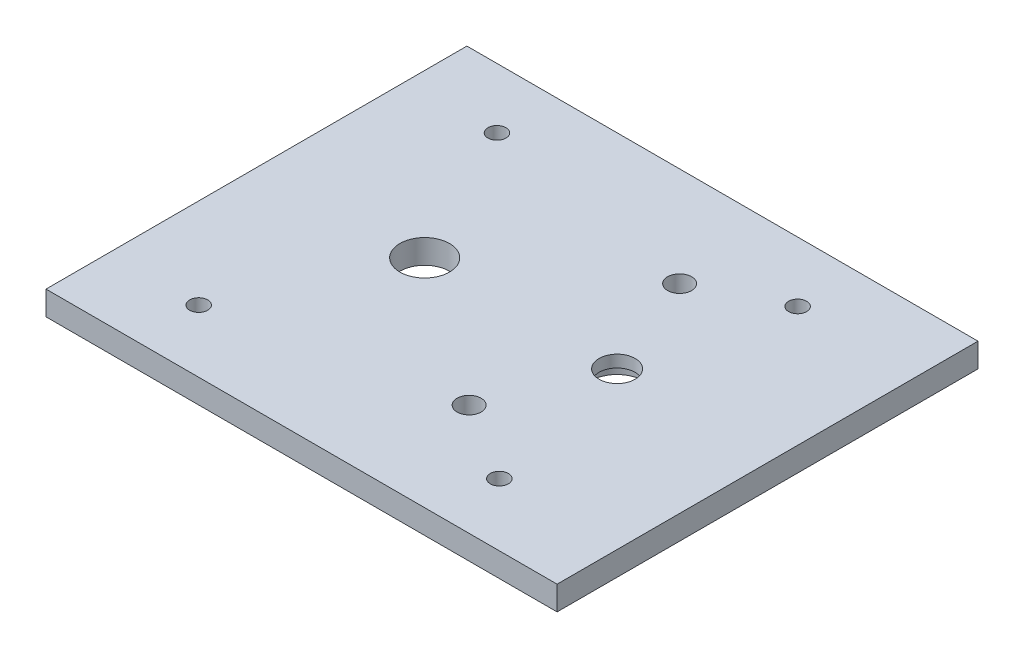
SolidWorks part; units mm, degrees
ref_plane "Front Plane" through (0, 0, 0) normal (0, 0, 1) x (1, 0, 0)
ref_plane "Top Plane" through (0, 0, 0) normal (0, 1, 0) x (1, 0, 0)
ref_plane "Right Plane" through (0, 0, 0) normal (1, 0, 0) x (0, 0, -1)
sketch "Sketch1" plane through (0, 0, 0) normal (0, 1, 0) x (1, 0, 0)
  line L0 (0, 8.2993) -> (0, -7.906) construction
  line L1 (-42.5, 35) -> (42.5, 35)
  line L2 (-42.5, 35) -> (-42.5, -35)
  line L3 (-42.5, -35) -> (42.5, -35)
  line L4 (42.5, 35) -> (42.5, -35)
  line L5 (-42.5, 35) -> (42.5, -35) construction
  line L6 (-42.5, -35) -> (42.5, 35) construction
  line L7 (-12.4915, 0.1967) -> (14.4413, 0.1967) construction
  line L8 (9.5, 1) -> (10.7497, 1) construction
  line L9 (37.5085, 0.1967) -> (64.4413, 0.1967) construction
  line L11 (15.0001, 2.9838) -> (15.0001, -1.0162)
  line L13 (17.9999, 3.0162) -> (17.9999, -0.9838)
  line L14 (15.0001, 2.9838) -> (17.9999, -0.9838) construction
  line L15 (15.0001, -1.0162) -> (17.9999, 3.0162) construction
  circle A0 centre (-27.5, 25) radius 1.5
  circle A1 centre (22.5, 25) radius 1.5
  circle A2 centre (22.5, -24.6067) radius 1.5
  circle A3 centre (-27.5, -24.6067) radius 1.5
  circle A4 centre (16.5, 1) radius 10
  circle A5 centre (-15.52, 1) radius 20
  arc A6 (15.0001, 2.9838) -> (17.9999, 3.0162) centre (16.5217, 1.0001) cw
  arc A7 (15.0001, -1.0162) -> (17.9999, -0.9838) centre (16.4783, 0.9999) ccw
  circle A8 centre (16.4783, 0.9999) radius 4.5
  circle A12 centre (-15.52, 1) radius 4.125
  circle A13 centre (16.4783, 0.9999) radius 3
  circle A14 centre (9.5, 1) radius 14
  circle A17 centre (85.0307, -10.8481) radius 14
  circle A18 centre (86.1334, -28.3481) radius 2
  circle A19 centre (86.1334, 6.6519) radius 2
  circle A20 centre (9.5, 1) radius 14
  circle A21 centre (9.4072, 18.471) radius 2
  circle A22 centre (9.4014, -16.529) radius 2
  point P0 (0, 0)
  point P46 (0, 0)
  dimension "D3" = 15
  dimension "D6" = 3
  dimension "D7" = 26
  dimension "D10" = 32.02
  dimension "D11" = 9
  dimension "D12" = 7
  dimension "D15" = 1.1027
  dimension "D17" = 1.1027
  dimension "D20" = 8.25
  dimension "D21" = 6
  dimension "D1" = 85
  dimension "D2" = 70
  dimension "D4" = 10
  dimension "D8" = 4
  dimension "D9" = 3
  dimension "D18" = 36
  dimension "D19" = 4
  dimension "D22" = 28.9915
  dimension "D5" = 2
extrude "Boss-Extrude4" add sketch "Sketch1" along normal blind 4 contours L4 L1 L2 L3 A14 A4 A5 A2 A1 A0 A3 | A14 A5 | A14 A4 | A5 A14 A4 | A5 A14 | A4 A14 A8 | A8 A13 | A4 A14 A5 region at (0, 0, -33.8989) region at (23.9705, 0, -1) region at (22.3127, 0, -5.9551) region at (6.1628, 0, -1) region at (-5.0421, 0, -1) region at (0.1582, 0, -1) region at (12.1056, 0, -0.9999)
sketch "Sketch2" plane through (0, 4, 0) normal (0, 1, 0) x (1, 0, 0)
  circle A3 centre (-15.52, 1) radius 9.125
  circle A4 centre (-15.52, 1) radius 9.125
  dimension "D1" = 5
extrude "Cut-Extrude2" cut sketch "Sketch1<7>" along normal blind 2 contours A8
sketch "Sketch1<7>" plane through (0, 0, 0) normal (0, 1, 0) x (1, 0, 0) same geometry as "Sketch1"
